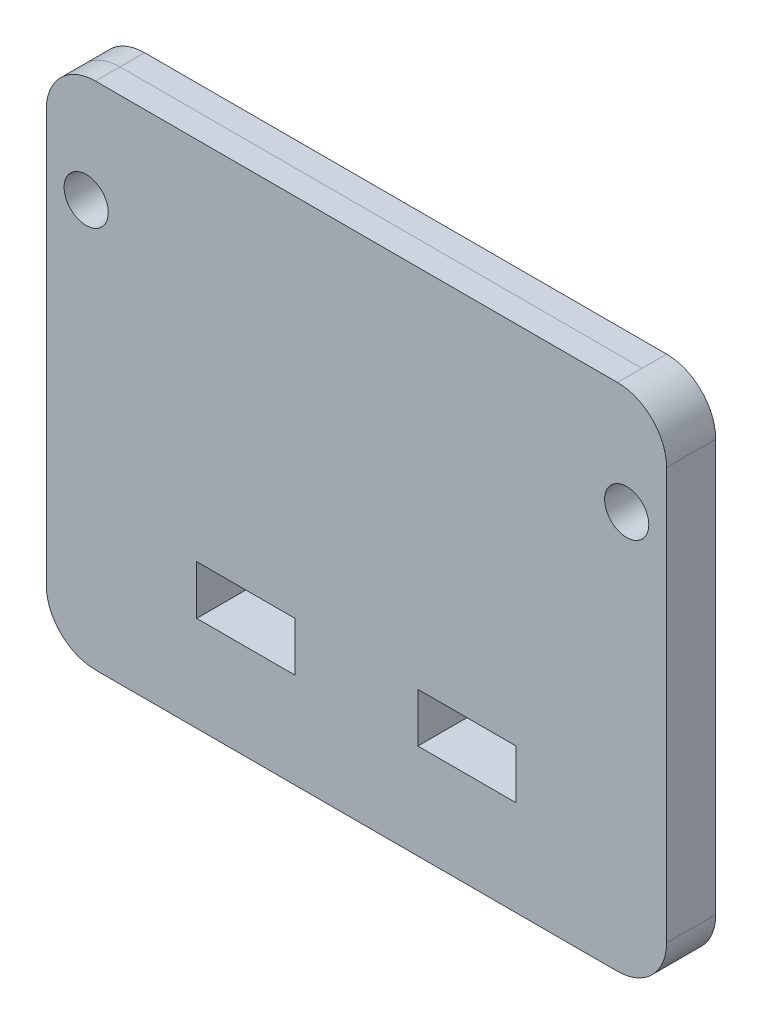
SolidWorks part; units mm, degrees
material "Pink Foam"
ref_plane "Front Plane" through (0, 0, 0) normal (0, 0, 1) x (1, 0, 0)
ref_plane "Top Plane" through (0, 0, 0) normal (0, 1, 0) x (1, 0, 0)
ref_plane "Right Plane" through (0, 0, 0) normal (1, 0, 0) x (0, 0, -1)
sketch "Sketch1" plane through (0, 0, 0) normal (0, 0, 1) x (1, 0, 0)
  line L1 (-139.7, -203.2) -> (139.7, -203.2) construction
  line L2 (-165.1, -177.8) -> (-165.1, 177.8) construction
  line L3 (-139.7, 203.2) -> (139.7, 203.2) construction
  line L4 (165.1, -177.8) -> (165.1, 177.8) construction
  line L5 (-165.1, -203.2) -> (165.1, 203.2) construction
  line L6 (-165.1, 203.2) -> (165.1, -203.2) construction
  line L7 (-134.9375, -131.8019) -> (134.9375, -131.8019)
  line L8 (-160.3375, -106.4019) -> (-160.3375, 106.4019)
  line L9 (-134.9375, 131.8019) -> (134.9375, 131.8019)
  line L10 (160.3375, -106.4019) -> (160.3375, 106.4019)
  line L11 (-160.3375, -131.8019) -> (160.3375, 131.8019) construction
  line L12 (-160.3375, 131.8019) -> (160.3375, -131.8019) construction
  arc A0 (-139.7, -203.2) -> (-165.1, -177.8) centre (-139.7, -177.8) cw construction
  arc A1 (139.7, -203.2) -> (165.1, -177.8) centre (139.7, -177.8) ccw construction
  arc A2 (139.7, 203.2) -> (165.1, 177.8) centre (139.7, 177.8) cw construction
  arc A3 (-165.1, 177.8) -> (-139.7, 203.2) centre (-139.7, 177.8) cw construction
  circle A4 centre (-139.7, 76.2) radius 11.422
  circle A5 centre (139.7, 76.2) radius 11.422
  arc A6 (-134.9375, -131.8019) -> (-160.3375, -106.4019) centre (-134.9375, -106.4019) cw
  arc A7 (134.9375, -131.8019) -> (160.3375, -106.4019) centre (134.9375, -106.4019) ccw
  arc A8 (134.9375, 131.8019) -> (160.3375, 106.4019) centre (134.9375, 106.4019) cw
  arc A9 (-160.3375, 106.4019) -> (-134.9375, 131.8019) centre (-134.9375, 106.4019) cw
  point P0 (0, 0)
  point P23 (0, 0)
  dimension "D3" = 25.4
  dimension "D7" = 22.844
  dimension "D8" = 320.6749
  dimension "D10" = 25.4
  dimension "D1" = 330.2
  dimension "D2" = 406.4
  dimension "D4" = 25.4
  dimension "D5" = 127
  dimension "D6" = 25.4
  dimension "D9" = 263.6038
extrude "Boss-Extrude1" add sketch "Sketch1" along normal blind 25.4
ref_plane "Plane1" through (0, 0, 12.7) normal (0, 0, 1) x (1, 0, 0)
sketch "Sketch2" plane through (0, 0, 0) normal (0, 0, -1) x (-1, 0, 0)
  line L16 (-82.55, -82.55) -> (-31.75, -82.55)
  line L17 (-31.75, -82.55) -> (-31.75, -57.15)
  line L18 (-31.75, -57.15) -> (-82.55, -57.15)
  line L19 (-82.55, -57.15) -> (-82.55, -82.55)
  line L24 (31.75, -82.55) -> (82.55, -82.55)
  line L25 (31.75, -57.15) -> (31.75, -82.55)
  line L26 (82.55, -57.15) -> (31.75, -57.15)
  line L27 (82.55, -82.55) -> (82.55, -57.15)
  dimension "D1" = 31.75
  dimension "D2" = 82.55
  dimension "D3" = 31.75
  dimension "D4" = 57.15
  dimension "D5" = 82.55
extrude "Foam Insert Cut-Throughs" cut sketch "Sketch2" against normal blind 25.4
split line "Split Line1"
